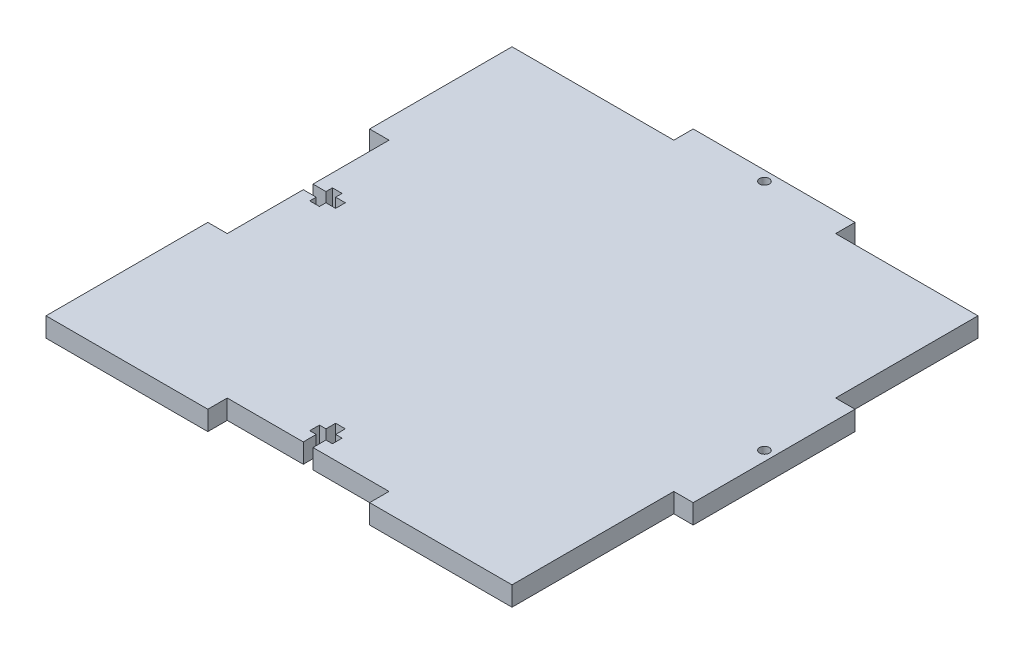
SolidWorks part; units mm, degrees
material "Acrylic (Medium-high impact)"
ref_plane "Front Plane" through (0, 0, 0) normal (0, 0, 1) x (1, 0, 0)
ref_plane "Top Plane" through (0, 0, 0) normal (0, 1, 0) x (1, 0, 0)
ref_plane "Right Plane" through (0, 0, 0) normal (1, 0, 0) x (0, 0, -1)
sketch "Sketch1" plane through (0, 0, 0) normal (0, 1, 0) x (1, 0, 0)
  line L0 (-72, 28) -> (-66, 28)
  line L1 (-72, -72) -> (72, -72)
  line L2 (-72, -72) -> (-72, 72)
  line L3 (-72, 72) -> (72, 72)
  line L4 (72, -72) -> (72, 72)
  line L5 (-72, -72) -> (72, 72) construction
  line L6 (-72, 72) -> (72, -72) construction
  line L7 (-66, 28) -> (-66, -22)
  line L8 (28, -72) -> (28, -66)
  line L9 (-22, 72) -> (-22, 78)
  line L10 (-22, 78) -> (28, 78)
  line L11 (28, 72) -> (28, 78)
  line L12 (72, 28) -> (78, 28)
  line L13 (78, 28) -> (78, -22)
  line L14 (-22, -72) -> (-22, -66)
  line L15 (-22, -66) -> (28, -66)
  line L16 (3, 78) -> (3, -72) construction
  line L17 (-72, 3) -> (78, 3) construction
  line L18 (72, -22) -> (78, -22)
  line L19 (-72, -22) -> (-66, -22)
  line L20 (75, 28) -> (75, -22) construction
  line L21 (4.5, -66) -> (4.5, -62)
  line L22 (4.5, -62) -> (6.5, -62)
  line L23 (6.5, -62) -> (6.5, -59)
  line L24 (6.5, -59) -> (4.5, -59)
  line L25 (4.5, -59) -> (4.5, -56)
  line L26 (4.5, -56) -> (1.5, -56)
  line L27 (1.5, -66) -> (1.5, -62)
  line L28 (1.5, -62) -> (-0.5, -62)
  line L29 (-0.5, -59) -> (1.5, -59)
  line L30 (-0.5, -62) -> (-0.5, -59)
  line L31 (1.5, -59) -> (1.5, -56)
  line L32 (-59, 4.5) -> (-56, 4.5)
  line L33 (-62, 4.5) -> (-62, 6.5)
  line L34 (-59, 6.5) -> (-59, 4.5)
  line L35 (-62, 6.5) -> (-59, 6.5)
  line L36 (-66, 4.5) -> (-62, 4.5)
  line L37 (-66, 1.5) -> (-62, 1.5)
  line L38 (-62, 1.5) -> (-62, -0.5)
  line L39 (-62, -0.5) -> (-59, -0.5)
  line L40 (-59, -0.5) -> (-59, 1.5)
  line L41 (-59, 1.5) -> (-56, 1.5)
  line L42 (-56, 4.5) -> (-56, 1.5)
  circle A0 centre (75, 3) radius 1.5
  circle A1 centre (3, 75) radius 1.5
  point P0 (0, 0)
  point P22 (3, 3)
  point P27 (3, 3)
  point P40 (3, -66)
  point P45 (-66, 3)
  point P49 (3, -56)
  dimension "D4" = 3
  dimension "D1" = 144
  dimension "D2" = 25
  dimension "D3" = 6
  dimension "D5" = 4
  dimension "D6" = 2
  dimension "D7" = 3
  dimension "D8" = 1.5
extrude "Boss-Extrude1" add sketch "Sketch1" along normal blind 6 contours L19 L2 L1 L14 L15 L8 L4 L3 L0 L7 | L3 L11 L10 L9 | L4 L18 L13 L12 region at (1.1086, 0, -1.1086) region at (-21.4964, 0, -75) region at (75, 0, -27.4964)
